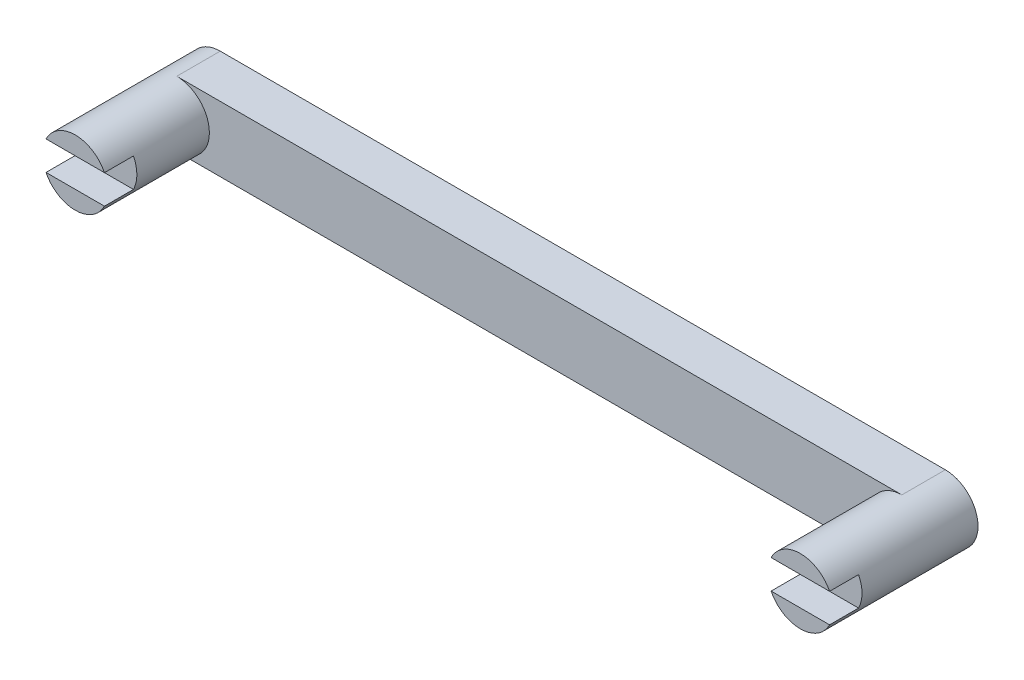
SolidWorks part; units mm, degrees
ref_plane "前视基准面" through (0, 0, 0) normal (0, 0, 1) x (1, 0, 0)
ref_plane "上视基准面" through (0, 0, 0) normal (0, 1, 0) x (1, 0, 0)
ref_plane "右视基准面" through (0, 0, 0) normal (1, 0, 0) x (0, 0, -1)
sketch "草图1" plane through (0, 0, 0) normal (0, 0, 1) x (1, 0, 0)
  line L0 (0, -2.25) -> (50, -2.25)
  line L1 (0, 0) -> (50, 0) construction
  line L2 (50, 2.25) -> (0, 2.25)
  circle A0 centre (0, 0) radius 2.25
  circle A1 centre (50, 0) radius 2.25
  point P9 (25.5696, -2.25)
  dimension "D1" = 4.5
  dimension "D2" = 50
extrude "凸台-拉伸1" add sketch "草图1" along normal blind 3 contours A0 | A0 L1 A1 L2 | L1 A0 L0 A1 | A1 region at (25, -1.1379, 0) region at (-2.1864, 0, 0) region at (48.454, -1.546, 0) region at (25, 1.1379, 0)
extrude "凸台-拉伸2" add sketch "草图1<3>" along normal blind 10 contours A0 | A1 region at (0, 0, 0) region at (50, 0, 0)
sketch "草图1<3>" plane through (0, 0, 0) normal (0, 0, 1) x (1, 0, 0) same geometry as "草图1"
sketch "草图2" plane through (0, 0, 10) normal (0, 0, 1) x (1, 0, 0)
  line L0 (0, 0) -> (50, 0) construction
  line L1 (-2.5, 1) -> (2.5, 1)
  line L2 (-2.5, 1) -> (-2.5, -1)
  line L3 (-2.5, -1) -> (2.5, -1)
  line L4 (2.5, 1) -> (2.5, -1)
  line L5 (-2.5, 1) -> (2.5, -1) construction
  line L6 (-2.5, -1) -> (2.5, 1) construction
  line L8 (47.5, 1) -> (52.5, 1)
  line L9 (47.5, 1) -> (47.5, -1)
  line L10 (47.5, -1) -> (52.5, -1)
  line L11 (52.5, 1) -> (52.5, -1)
  line L12 (47.5, 1) -> (52.5, -1) construction
  line L13 (47.5, -1) -> (52.5, 1) construction
  point P0 (0, 0)
  dimension "D1" = 2
  dimension "D2" = 5
  dimension "D3" = 5
  dimension "D4" = 2
extrude "切除-拉伸1" cut sketch "草图2" against normal blind 2
